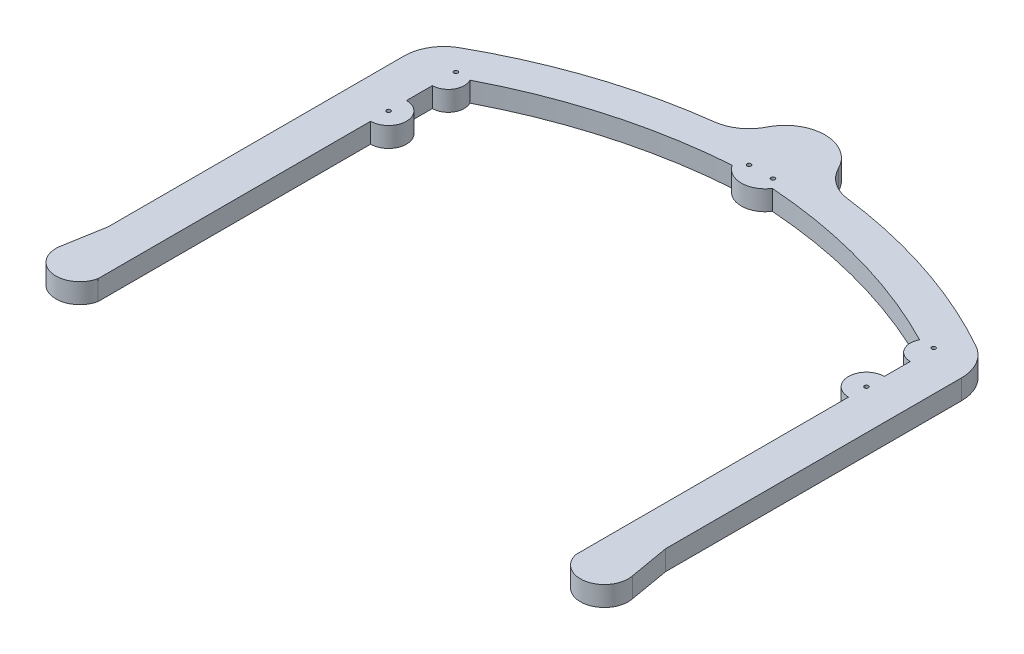
SolidWorks part; units mm, degrees
ref_plane "Front Plane" through (0, 0, 0) normal (0, 0, 1) x (1, 0, 0)
ref_plane "Top Plane" through (0, 0, 0) normal (0, 1, 0) x (1, 0, 0)
ref_plane "Right Plane" through (0, 0, 0) normal (1, 0, 0) x (0, 0, -1)
sketch "Sketch1" plane through (0, 0, 0) normal (0, 1, 0) x (1, 0, 0)
  line L0 (0, 0) -> (0, 117.2677) construction
  line L1 (70, 97.2677) -> (60, 92.6851) construction
  line L2 (70, 97.2677) -> (70, 17.2677)
  line L3 (60, 92.6851) -> (60, 4.7323)
  line L4 (0, 117.2677) -> (0, 127.2677) construction
  line L5 (0, 117.2677) -> (0, 109.2677)
  line L6 (0, 117.2677) -> (86.1145, 117.2677) construction
  line L7 (70, 17.2677) -> (71.7291, 7.2677)
  line L8 (0, 127.2677) -> (0, 117.2677)
  line L9 (0, 0) -> (125.6387, 0) construction
  line L10 (60, 4.7323) -> (71.7291, 7.2677) construction
  arc A0 (0, 117.2677) -> (70, 97.2677) centre (0, -15.2323) cw
  arc A1 (0, 109.2677) -> (60, 92.6851) centre (-4.309, -23.1622) cw
  arc A2 (0, 127.2677) -> (9.9929, 116.8903) centre (0, 117.2677) cw
  arc A3 (60, 4.7323) -> (71.7291, 7.2677) centre (65.8645, 6) ccw
  dimension "D4" = 10
  dimension "D9" = 6
  dimension "D1" = 8
  dimension "D2" = 20
  dimension "D3" = 70
  dimension "D5" = 10
  dimension "D6" = 11
  dimension "D7" = 170.19
  dimension "D8" = 10
  dimension "D10" = 100
extrude "Boss-Extrude2" add sketch "Sketch1" along normal blind 5 contours A2 L8 A0 | A0 L2 L7 A3 L3 A1 L5 region at (4.2954, 0, -121.4431)
fillet "Fillet2" radius 10 2 edges at (70, 2.5, -97.2677) (9.9929, 2.5, -116.8903)
sketch "Sketch2" plane through (0, 5, 0) normal (0, 1, 0) x (1, 0, 0)
  line L0 (0, 106.2677) -> (0, 109.2677)
  line L1 (60, 92.6851) -> (60, 4.7323) construction
  arc A0 (56.4738, 94.5735) -> (60, 88.6851) centre (60, 92.6851) ccw
  arc A1 (60, 82.1851) -> (60, 73.1851) centre (60, 77.6851) ccw
  arc A2 (5.0371, 109.0078) -> (0, 106.2677) centre (0, 112.2677) cw
  arc A7 (60, 92.6851) -> (0, 109.2677) centre (-4.309, -23.1622) ccw construction
  arc M7 (0, 109.2677) -> (60, 92.6851) centre (-4.309, -23.1622) cw
  line M8 (60, 92.6851) -> (60, 4.7323)
  dimension "D1" = 4
  dimension "D2" = 4.5
  dimension "D3" = 6
  dimension "D4" = 3
  dimension "D5" = 15
extrude "Boss-Extrude3" add sketch "Sketch2" against normal blind 5 contours A0 M7 M8 | A1 M8 | A2 L0 M7 region at (58.0901, 5, -77.6851) region at (58.097, 5, -91.5504) region at (1.95, 5, -107.9723)
hole_wizard "Ø1.0 (1) Diameter Hole1" positions "Sketch4" profile "Sketch3" hole size "Ø1.0" standard "ISO" end condition through all
sketch "Sketch4" plane through (0, 5, 0) normal (0, 1, 0) x (1, 0, 0)
  line L0 (0, 127.2677) -> (0, 106.2677) construction
  line L1 (60, 82.1851) -> (60, 73.1851) construction
  line L3 (60, 88.6851) -> (60, 94.5735) construction
  line L5 (56.4738, 94.5735) -> (60, 94.5735) construction
  point P0 (60, 77.6851)
  point P2 (60, 94.5735)
  point P4 (3, 111.21)
  dimension "D1" = 3
  dimension "D2" = 3
sketch "Sketch3" plane through (60, 5, -77.6851) normal (1, 0, 0) x (0, 0, 1)
  line L0 (0, 0) -> (0, 5)
  line L1 (0, 5) -> (0.5, 5)
  line L2 (0.5, 5) -> (0.5, 0)
  line L5 (0.5, 0) -> (0, 0)
  line L11 (0, -6.35) -> (0, 107.95) construction
  dimension "Thru Hole Dia." = 1
  dimension "Thru Hole Depth" = 5
mirror "Mirror2" about plane through (0, 5, 0) normal (1, 0, 0) of "Ø1.0 (1) Diameter Hole1", "Boss-Extrude3", "Fillet2", "Boss-Extrude2"
sketch "Sketch5" plane through (0, 5, 0) normal (0, 1, 0) x (1, 0, 0)
  line L0 (0, 114.21) -> (0, 72.5735) construction
  line L1 (0, 72.5735) -> (63.5, 72.5735) construction
  line L2 (0, 114.21) -> (63.5, 114.21) construction
  line L3 (63.5, 97.5735) -> (63.5, 72.5735)
  line L4 (0, 114.21) -> (0, 89.21)
  line L5 (0, 127.2677) -> (0, 106.2677) construction
  line L6 (60, 73.1851) -> (60, 4.7323) construction
  line L7 (63.5, 114.21) -> (63.5, 97.5735) construction
  arc A0 (0, 114.21) -> (63.5, 97.5735) centre (0, -15.2949) cw
  arc A1 (0, 89.21) -> (63.5, 72.5735) centre (0, -40.2949) cw
  arc A3 (8.9633, 121.7017) -> (-8.9633, 121.7017) centre (0, 117.2677) ccw construction
  arc A4 (-5.0371, 109.0078) -> (5.0371, 109.0078) centre (0, 112.2677) ccw construction
  circle A5 centre (60, 94.5735) radius 0.5 construction
  circle A7 centre (3, 111.21) radius 0.5 construction
  point P10 (3, 111.21)
  point P11 (60, 94.5735)
  point P12 (60, 77.6851)
  dimension "D4" = 3
  dimension "D1" = 25
  dimension "D2" = 3.5
  dimension "D3" = 3
  dimension "D5" = 63.5
  dimension "D6" = 41.6365
